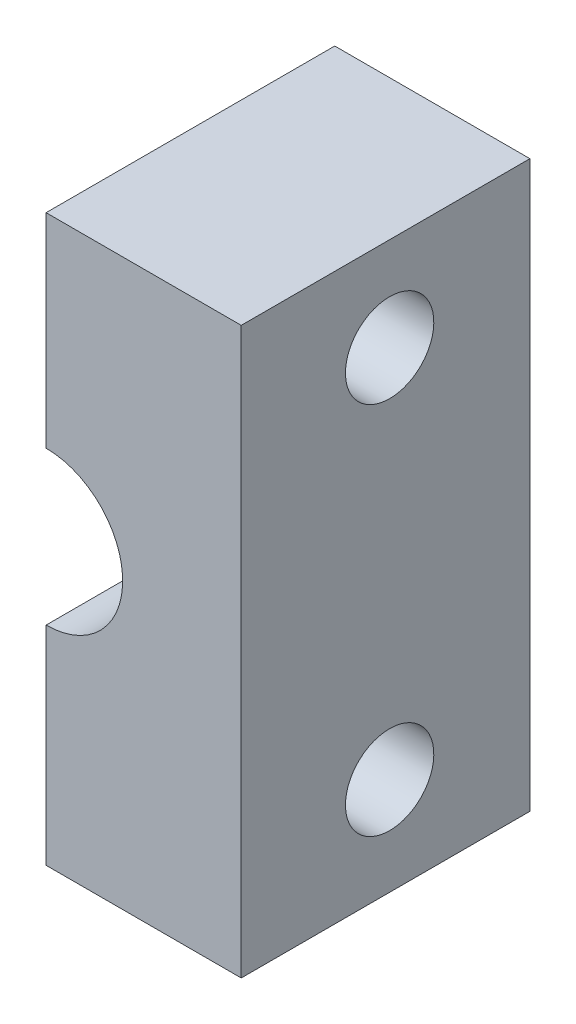
SolidWorks part; units mm, degrees
material "Pure Gold"
ref_plane "Front" through (0, 0, 0) normal (0, 0, 1) x (1, 0, 0)
ref_plane "Top" through (0, 0, 0) normal (0, 1, 0) x (1, 0, 0)
ref_plane "Right" through (0, 0, 0) normal (1, 0, 0) x (0, 0, -1)
sketch "Sketch4" plane through (0, 0, 0) normal (0, 0, 1) x (1, 0, 0)
  line L0 (0, -42.8625) -> (0, 41.275) construction
  line L1 (-49.15, -15.5) -> (-80.15, 15.5) construction
  line L2 (-80.15, -15.5) -> (-49.15, 15.5) construction
  line L3 (-39.925, 44.5615) -> (-39.925, -66.5635) construction
  line L4 (-71.275, 44.5615) -> (-71.275, -66.5635) construction
  line L8 (-62.05, 15.5) -> (-31.05, -15.5) construction
  line L9 (-31.05, 15.5) -> (-62.05, -15.5) construction
  line L11 (-31.05, 36.624) -> (-31.05, -53.8635) construction
  line L12 (43.75, 0) -> (-164.4633, 0) construction
  line L13 (-62.05, 36.624) -> (-62.05, -53.8635) construction
  line L14 (-49.15, 36.624) -> (-49.15, -53.8635) construction
  line L15 (-80.15, 36.624) -> (-80.15, -53.8635) construction
  line L16 (-113.2228, 15.5) -> (-0.2036, 15.5) construction
  line L17 (-113.2228, -15.5) -> (-0.2036, -15.5) construction
  line L18 (-25, -66.5635) -> (-25, 44.5615) construction
  line L19 (-68.1, -66.5635) -> (-68.1, 44.5615) construction
  line L20 (-43.1, 44.5615) -> (-43.1, -66.5635) construction
  line L21 (-86.2, -66.5635) -> (-86.2, 44.5615) construction
  line L22 (5.8397, -21.55) -> (-134.1626, -21.55) construction
  line L23 (5.8397, 21.55) -> (-134.1626, 21.55) construction
  line L24 (10.9249, -24.725) -> (-138.6228, -24.725) construction
  line L25 (10.9249, 24.725) -> (-138.6228, 24.725) construction
  line L26 (-89.375, 44.5615) -> (-89.375, -66.5635) construction
  line L27 (-21.825, 44.5615) -> (-21.825, -66.5635) construction
  circle A0 centre (0, 0) radius 12.7 construction
  circle A1 centre (0, 0) radius 15.875 construction
  circle A2 centre (0, 0) radius 9.46 construction
  circle A3 centre (-93.65, 0) radius 9.46 construction
  arc A4 (-93.65, 12.7) -> (-93.65, -12.7) centre (-93.65, 0) ccw construction
  circle A5 centre (27.27, 0) radius 9.46 construction
  circle A6 centre (27.27, 0) radius 12.7 construction
  circle A7 centre (-120.3675, 0) radius 9.46 construction
  circle A8 centre (-120.3675, 0) radius 12.7 construction
  point P3 (0, 0)
  point P6 (-49.15, -15.5)
  point P11 (-93.65, 0)
  point P12 (-49.15, 15.5)
  point P13 (-46.55, 0)
  point P14 (-80.15, 15.5)
  point P15 (-80.15, -15.5)
  point P61 (-64.65, 0)
  point P65 (27.27, 0)
  point P66 (-120.3675, 0)
  dimension "D20" = 3.175
  dimension "D18" = 29
  dimension "D26" = 73.82
  dimension "D27" = 64.65
  dimension "D2" = 31
  dimension "D3" = 25
  dimension "D4" = 31
  dimension "D5" = 21.825
  dimension "D6" = 15.5
  dimension "D7" = 15.5
  dimension "D8" = 6.05
  dimension "D9" = 6.05
  dimension "D10" = 6.05
  dimension "D11" = 6.05
  dimension "D12" = 6.05
  dimension "D13" = 6.05
  dimension "D14" = 3.175
  dimension "D15" = 3.175
  dimension "D16" = 3.175
  dimension "D17" = 3.175
  dimension "D19" = 3.175
  dimension "D21" = 3.175
  dimension "D22" = 46.55
  dimension "D23" = 47.1
  dimension "D24" = 58.32
  dimension "D25" = 147.6375
sketch "Sketch5" plane through (0, 0, 0) normal (0, 0, 1) x (1, 0, 0)
  line L0 (-46.55, 1.6) -> (-46.55, -2.6) construction
  line L4 (-46.55, -2.6) -> (-46.55, -9.6636)
  line L5 (-46.55, 9.525) -> (-39.925, 9.525)
  line L7 (-39.925, 44.5615) -> (-39.925, -66.5635) construction
  line L8 (-39.925, -9.6636) -> (-39.925, 9.525)
  line L9 (-46.55, -9.6636) -> (-39.925, -9.6636)
  line L13 (-46.55, 9.525) -> (-46.55, 2.6)
  circle A0 centre (-46.55, 0) radius 2.6 construction
  arc A1 (-46.55, 2.6) -> (-46.55, -2.6) centre (-46.55, 0) cw
extrude "Extrude1" add sketch "Sketch5" along normal blind 9.8
sketch "Sketch7" plane through (-39.925, 0, 0) normal (1, 0, 0) x (0, 0, -1)
  circle A0 centre (-4.7625, 6.35) radius 1.5
  circle A1 centre (-4.7625, -6.35) radius 1.5
extrude "Extrude3" cut sketch "Sketch7" against normal up to surface (6.625 mm away) up to face at (-46.55, 6.0625, 4.9)
